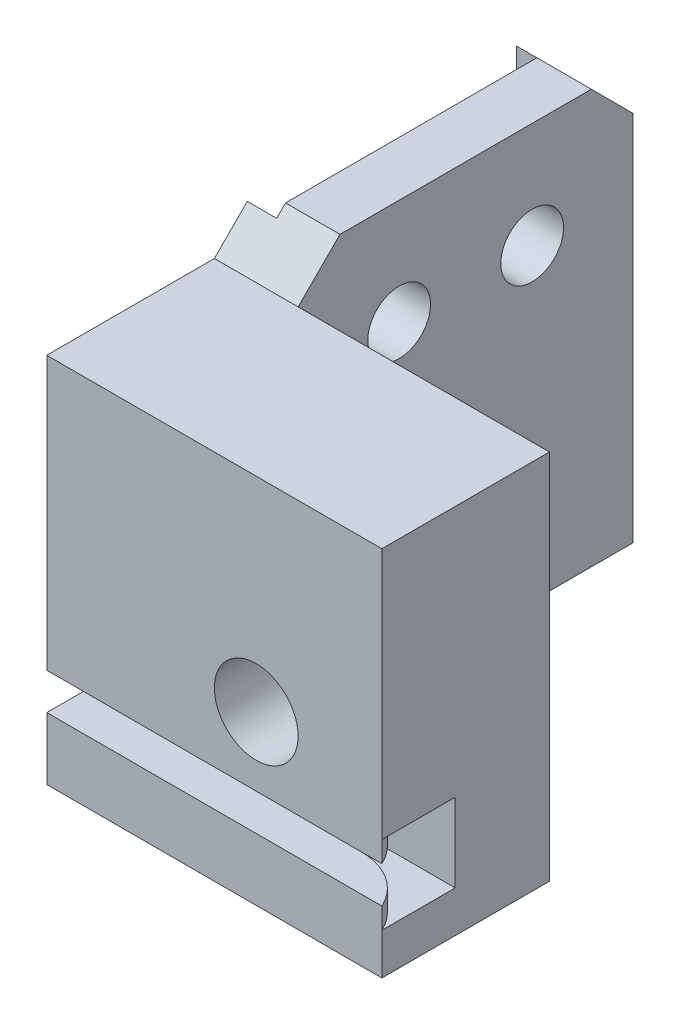
SolidWorks part; units mm, degrees
other "Markup1"
sketch "Sketch3" plane through (0, 0, 24) normal (-0.9768, -0.0702, 0.2026) x (0.2071, -0.0648, 0.9762)
ref_plane "Front Plane" through (0, 0, 0) normal (0, 0, 1) x (1, 0, 0)
ref_plane "Top Plane" through (0, 0, 0) normal (0, 1, 0) x (1, 0, 0)
ref_plane "Right Plane" through (0, 0, 0) normal (1, 0, 0) x (0, 0, -1)
sketch "ProfileSketch2" plane through (0, 0, 0) normal (0, 1, 0) x (1, 0, 0)
  line L0 (0, 0) -> (0, -24)
  line L1 (0, -24) -> (16, -24)
  line L5 (16, -16) -> (4, -16)
  line L6 (4, -16) -> (4, 0)
  line L7 (4, 0) -> (0, 0)
  line L8 (16, -16) -> (16, -24)
  dimension "D1" = 16
  dimension "D2" = 4
  dimension "D3" = 16
  dimension "D4" = 24
extrude "ProfileBoss-Extrude1" add sketch "ProfileSketch2" along normal blind 19.75
sketch "MicroSwitchHoleSketch3" plane through (0, 0, 0) normal (-1, 0, 0) x (0, 0, 1)
  line L0 (0, 19.75) -> (24, 19.75) construction
  line L1 (1.575, 19.75) -> (14.425, 19.75)
  line L2 (1.575, 19.75) -> (1.575, 7.7)
  line L3 (1.575, 7.7) -> (14.425, 7.7)
  line L4 (14.425, 19.75) -> (14.425, 7.7)
  line L6 (0, 19.75) -> (0, 0) construction
  dimension "D1" = 12.85
  dimension "D2" = 12.05
  dimension "D4" = 1.575
extrude "MicroSwitchHoleCut-Extrude1" cut sketch "MicroSwitchHoleSketch3" against normal blind 1.4
sketch "MicroSwitchHoleSketch4" plane through (1.4, 0, 0) normal (-1, 0, 0) x (0, 0, 1)
  line L0 (1.575, 19.75) -> (1.575, 7.7) construction
  line L1 (14.425, 7.7) -> (14.425, 19.75) construction
  line L2 (1.575, 7.7) -> (14.425, 7.7) construction
  circle A0 centre (4.825, 14.7) radius 1.5
  circle A1 centre (11.175, 14.7) radius 1.5
  dimension "D1" = 3
  dimension "D2" = 3.25
  dimension "D3" = 3.25
  dimension "D4" = 7
extrude "MicroSwitchHoleCut-Extrude2" cut sketch "MicroSwitchHoleSketch4" against normal blind 3
sketch "LongWireChannelSketch7" plane through (0, 0, 0) normal (-1, 0, 0) x (0, 0, 1)
  line L0 (24, 4.725) -> (22.25, 4.725)
  line L1 (24, 19.75) -> (24, 0) construction
  line L2 (22.25, 4.725) -> (22.25, 5.725)
  line L3 (22.25, 5.725) -> (20.5, 5.725)
  line L4 (20.5, 5.725) -> (20.5, 1.975)
  line L5 (20.5, 1.975) -> (22.25, 1.975)
  line L6 (22.25, 1.975) -> (22.25, 2.975)
  line L7 (22.25, 2.975) -> (24, 2.975)
  line L8 (24, 2.975) -> (24, 4.725)
  line L9 (1.575, 7.7) -> (14.425, 7.7) construction
  dimension "D1" = 1.75
  dimension "D2" = 3.75
  dimension "D3" = 1.75
  dimension "D4" = 1.975
extrude "LongWireChannelCut-Extrude5" cut sketch "LongWireChannelSketch7" against normal through all
sketch "ShortWireChannelSketch8" plane through (0, 0, 0) normal (-1, 0, 0) x (0, 0, 1)
  line L0 (6.125, 7.7) -> (6.125, 1.975)
  line L1 (6.125, 1.975) -> (20.5, 1.975)
  line L2 (20.5, 5.725) -> (20.5, 1.975) construction
  line L3 (20.5, 1.975) -> (20.5, 5.725)
  line L4 (20.5, 5.725) -> (9.875, 5.725)
  line L5 (9.875, 5.725) -> (9.875, 7.7)
  line L6 (1.575, 7.7) -> (14.425, 7.7) construction
  line L7 (9.875, 7.7) -> (6.125, 7.7)
  line L8 (22.25, 5.725) -> (20.5, 5.725) construction
  line L11 (20.5, 1.975) -> (22.25, 1.975) construction
  line L12 (1.575, 7.7) -> (14.425, 7.7) construction
  line L13 (0, 19.75) -> (0, 0) construction
  dimension "D1" = 6.125
extrude "ShortWireChannelCut-Extrude6" cut sketch "ShortWireChannelSketch8" against normal blind 1.4
fillet "Fillet1" radius 2.2 1 edges at (1.4, 3.85, 20.5)
sketch "LinearRaukHoleSketch1" plane through (0, 0, 24) normal (0, 0, 1) x (1, 0, 0)
  line L1 (0, 0) -> (16, 0) construction
  line L2 (16, 19.75) -> (16, 4.725) construction
  circle A0 centre (10, 8) radius 2
  dimension "D1" = 4
  dimension "D3" = 8
  dimension "D2" = 6
extrude "LinearRailHoleCut-Extrude1" cut sketch "LinearRaukHoleSketch1" against normal through all
fillet "Fillet2" radius 3 2 edges at (0.7, 5.725, 9.875) (0.7, 7.7, 6.125)
fillet "Fillet3" radius 3 2 edges at (16, 2.475, 22.25) (16, 5.225, 22.25)
sketch "Sketch2" plane through (0, 0, 24) normal (0, 0, 1) x (1, 0, 0)
  line L0 (16, 19.75) -> (16, 5.725) construction
  line L1 (0, 19.75) -> (16, 19.75)
  line L2 (0, 19.75) -> (0, 17.75)
  line L3 (0, 17.75) -> (16, 17.75)
  line L4 (16, 19.75) -> (16, 17.75)
  dimension "D1" = 2
extrude "KnotchCut-Extrude2" cut sketch "Sketch2" against normal blind 8
chamfer "Chamfer1" distance 2 angle 45 2 edges at (2, 19.75, 16) (2, 19.75, 0)
equation "\"LinearRailWidth\"= 12mm'Spec"
equation "\"LinearRailHeight\"= 8mm'Spec"
equation "\"LinearRailHoleDiameter\"= 3.5mm'Spec"
equation "\"LinearRailHoleDistance\"= 25mm'Spec"
equation "\"LinearRailSupportNutWidth\"= 6.2mm"
equation "\"LinearRailSupportNutHoleDepth\"= \"LinearRailHeight\" / 4"
equation "\"M2HeatInsertDiameter\"= 3mm'Spec"
equation "\"M2HeatInsertHoleDepth\"= 3mm"
equation "\"MicroSwitchMountingHoleOffsetFromBottom\"= 1.5mm"
equation "\"MicroSwitchTerminalHeight\"= 3.5mm"
equation "\"MicroSwitchDepth\"= 2.8mm"
equation "\"MicroSwitchLength\"= 12.85mm"
equation "\"MicroSwitchHeight\"= 6.55mm"
equation "\"MicroSwitchMountingHoleOffsetFromSide\"= 3.25mm"
equation "\"D1@MicroSwitchHoleSketch3\" = \"MicroSwitchLength\""
equation "\"D2@MicroSwitchHoleSketch3\"=\"MicroSwitchMountingHoleHeight\""
equation "\"MicroSwitchExtraMountingHeight\"= 2mm"
equation "\"D1@MicroSwitchHoleCut-Extrude1\"=\"MicroSwitchDepth\" / 2"
equation "\"D1@MicroSwitchHoleSketch4\" = \"M2HeatInsertDiameter\""
equation "\"D2@MicroSwitchHoleSketch4\" = \"MicroSwitchMountingHoleOffsetFromSide\""
equation "\"D4@MicroSwitchHoleSketch4\" = \"MicroSwitchExtraMountingHeight\" + \"MicroSwitchTerminalHeight\" + \"MicroSwitchMountingHoleOffsetFromBottom\""
equation "\"D1@MicroSwitchHoleCut-Extrude2\" = \"M2HeatInsertHoleDepth\""
equation "\"XAxisMicroSwitchClampHeight\"= \"LinearRailWidth\" + \"LinearRailHeight\" / 2"
equation "\"XAxisMicroSwitchClampWidth\"= \"LinearRailHeight\" + \"LinearRailHeight\" + \"LinearRailHeight\""
equation "\"XAxisMicroSwitchClampDepth\"= \"LinearRailHeight\" * 2 + \"EndStopCableWidth\""
equation "\"M3HeatInsertHoleDiameter\"= 4mm'Spec"
equation "\"M3HeatInsertHoleDepth\"= 4.1mm"
equation "\"D1@ProfileBoss-Extrude1\"=\"XAxisMicroSwitchClampDepth\""
equation "\"MicroSwitchMountingHoleHeight\"= \"MicroSwitchExtraMountingHeight\" + \"MicroSwitchTerminalHeight\" + \"MicroSwitchHeight\""
equation "\"D4@LongWireChannelSketch7\"=( \"XAxisMicroSwitchClampDepth\" - \"MicroSwitchMountingHoleHeight\" - \"EndStopCableWidth\")  / 2"
equation "\"D1@ShortWireChannelSketch8\"=( \"XAxisMicroSwitchClampHeight\" - \"EndStopCableWidth\" )  / 2"
equation "\"D1@ShortWireChannelCut-Extrude6\"=\"MicroSwitchDepth\"/ 2"
equation "\"EndStopCableDepth\"= 1.75mm"
equation "\"EndStopCableWidth\"= 3.75mm"
equation "\"D1@LongWireChannelSketch7\"=\"EndStopCableDepth\""
equation "\"D2@LongWireChannelSketch7\"=\"EndStopCableWidth\""
equation "\"D3@LongWireChannelSketch7\"=\"EndStopCableDepth\""
equation "\"D1@ProfileSketch2\"=\"LinearRailHeight\" * 2"
equation "\"D2@ProfileSketch2\"=\"LinearRailHeight\"/2"
equation "\"D3@ProfileSketch2\"=\"XAxisMicroSwitchClampHeight\""
equation "\"D4@ProfileSketch2\"=\"XAxisMicroSwitchClampWidth\""
equation "\"D1@LinearRaukHoleSketch1\" = \"M3HeatInsertHoleDiameter\""
equation "\"D3@LinearRaukHoleSketch1\" = \"XAxisMicroSwitchClampHeight\" / 2"
equation "\"D2@LinearRaukHoleSketch1\"=\"LinearRailWidth\"/2"
